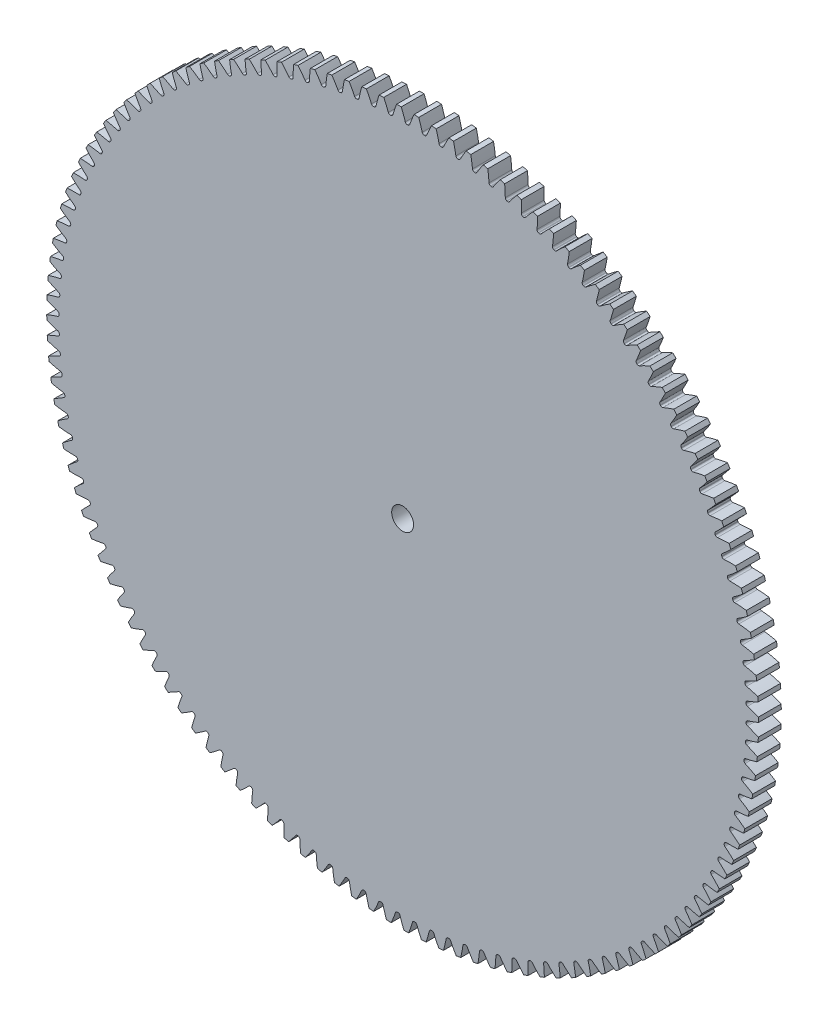
SolidWorks part; units mm, degrees
ref_plane "Front" through (0, 0, 0) normal (0, 0, 1) x (1, 0, 0)
ref_plane "Top" through (0, 0, 0) normal (0, 1, 0) x (1, 0, 0)
ref_plane "Right" through (0, 0, 0) normal (1, 0, 0) x (0, 0, -1)
sketch "Sketch3" plane through (0, 0, 0) normal (0, 0, 1) x (1, 0, 0)
  circle A0 centre (0, 0) radius 51.5938
  dimension "od" = 103.1875
extrude "gearBody" add sketch "Sketch3" along normal blind 3.302
sketch "Sketch2" plane through (0, 0, 0) normal (0, 0, 1) x (1, 0, 0)
  line L0 (0, 0) -> (44.1027, 18.2679) construction
  line L1 (60.0354, -8.954) -> (0, 0) construction
  line L2 (0, 0) -> (36.3143, 0) construction
  line L3 (50.7999, -0.1147) -> (50.7826, -1.3294) construction
  line L5 (50.7912, -0.722) -> (0, 0) construction
  line L7 (0, 0) -> (47.7364, 0) construction
  arc A0 (47.7268, -0.958) -> (47.7347, -0.399) centre (0, 0) ccw construction
  arc A1 (51.5934, 0.1942) -> (51.567, -1.6607) centre (0, 0) ccw construction
  arc A2 (50.7999, -0.1147) -> (50.7826, -1.3294) centre (0, 0) ccw construction
  arc A3 (49.7911, -0.7449) -> (49.7922, -0.6708) centre (0, 0) ccw
  arc A4 (60.0354, -8.954) -> (49.995, -1.0362) centre (43.5656, -19.5142) ccw
  arc A5 (60.0354, -8.954) -> (60.2656, 7.2438) centre (0, 0) ccw
  arc A6 (60.2656, 7.2438) -> (50.0042, -0.3853) centre (44.1027, 18.2679) cw
  arc A7 (49.7922, -0.6708) -> (50.0042, -0.3853) centre (50.0958, -0.6749) cw
  arc A8 (49.995, -1.0362) -> (49.7911, -0.7449) centre (50.0948, -0.7494) cw
  point P6 (60.2656, 7.2438)
  point P22 (60.0354, -8.954)
  dimension "baseDia" = 95.4728
  dimension "od" = 103.1875
  dimension "pd" = 101.6
  dimension "rd" = 99.5934
  dimension "rFillet" = 0.3037
  dimension "pointX" = 60.2656
  dimension "pointY" = 7.2438
  dimension "CTT" = 1.2148
  dimension "flankCenterAngle" = 22.5
extrude "toothCut" cut sketch "Sketch2" along normal through all
pattern_circular "CirPattern1" count 128 over 360 about axis through (0, 0, 0) along (0, 0, 1) of "toothCut"
sketch "hub1Dia" plane through (0, 0, 0) normal (0, 0, -1) x (-1, 0, 0)
  circle A0 centre (0, 0) radius 12.7
  dimension "hub1Dia" = 25.4
sketch "hub2Dia" plane through (0, 0, 3.302) normal (0, 0, 1) x (1, 0, 0)
  circle A0 centre (0, 0) radius 12.7
  dimension "hub2dia" = 25.4
sketch "boreDia" plane through (0, 0, 0) normal (0, 0, 1) x (1, 0, 0)
  circle A0 centre (0, 0) radius 1.5875
  dimension "boreDia" = 3.175
extrude "bore" cut sketch "boreDia" against normal mid plane 25400
